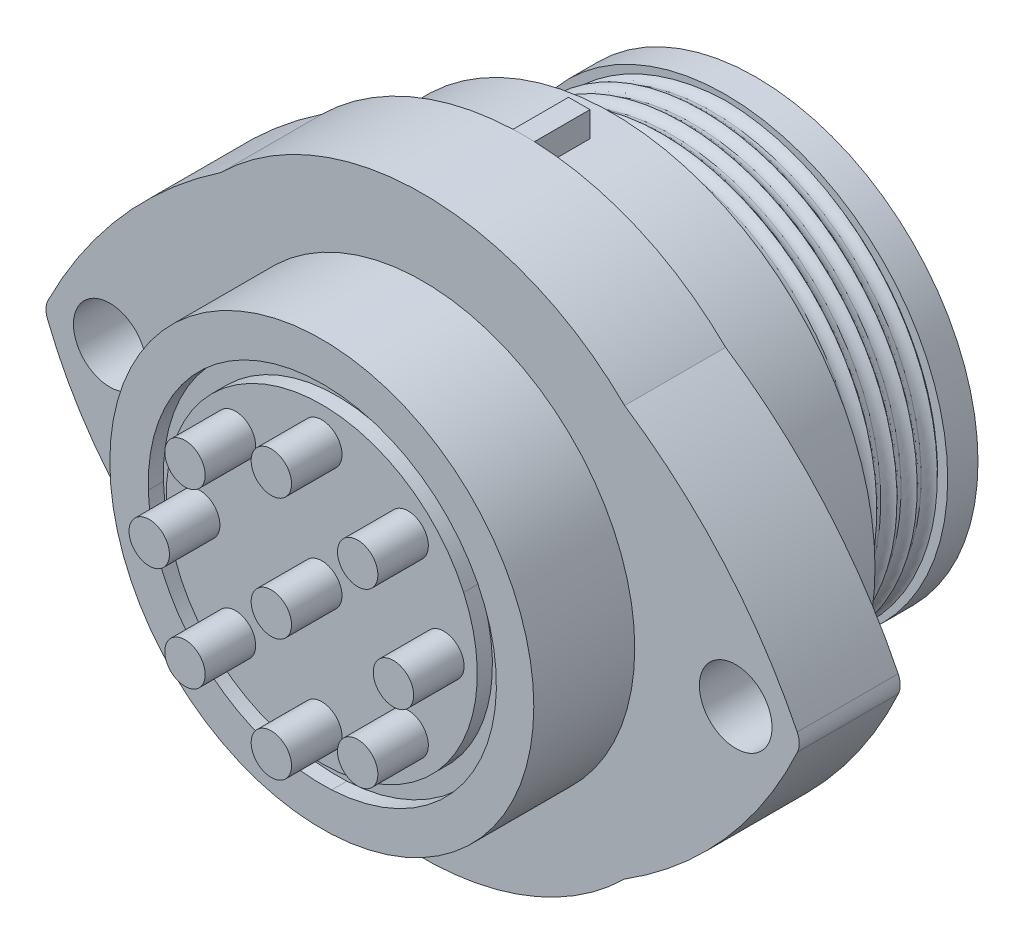
SolidWorks part; units mm, degrees
ref_plane "Front Plane" through (0, 0, 0) normal (0, 0, 1) x (1, 0, 0)
ref_plane "Top Plane" through (0, 0, 0) normal (0, 1, 0) x (1, 0, 0)
ref_plane "Right Plane" through (0, 0, 0) normal (1, 0, 0) x (0, 0, -1)
sketch "Sketch1" plane through (0, 0, 0) normal (0, 0, 1) x (1, 0, 0)
  circle A0 centre (0, 0) radius 10.5
  dimension "D1" = 21
extrude "Boss-Extrude1" add sketch "Sketch1" along normal blind 5
sketch "Sketch2" plane through (0, 0, 0) normal (0, 0, 1) x (1, 0, 0)
  arc A12 (9.9974, 10.1546) -> (-9.9974, 10.1546) centre (0, 0) ccw
  arc A13 (9.9974, 10.1546) -> (18.75, 0) centre (-3.668, -10.4735) cw
  arc A14 (18.75, 0) -> (9.9974, -10.1546) centre (-2.0445, 9.0742) cw
  arc A15 (-9.9974, 10.1546) -> (-18.75, 0) centre (4.3482, -11.0599) ccw
  arc A16 (-9.9974, -10.1546) -> (-18.75, 0) centre (-0.8564, 6.5738) cw
  arc A17 (-9.9974, -10.1546) -> (9.9974, -10.1546) centre (0, 0) ccw
  dimension "D1" = 28.5
  dimension "D2" = 18.75
  dimension "D3" = 18.75
extrude "Boss-Extrude2" add sketch "Sketch2" against normal blind 5
sketch "Sketch3" plane through (0, 0, -5) normal (0, 0, -1) x (-1, 0, 0)
  circle A2 centre (-15.5, 0) radius 1.8
  circle A3 centre (15.5, 0) radius 1.8
  dimension "D1" = 3.6
  dimension "D2" = 3.6
extrude "Cut-Extrude1" cut sketch "Sketch3" against normal blind 5
fillet "Fillet1" radius 1 2 edges at (-18.75, 0, -2.5) (18.75, 0, -2.5)
sketch "Sketch4" plane through (0, 0, 5) normal (0, 0, 1) x (1, 0, 0)
  circle A0 centre (0, 0) radius 1
  dimension "D1" = 2
extrude "Boss-Extrude5" add sketch "Sketch4" along normal blind 2.5
sketch "Sketch6" plane through (0, 0, 5) normal (0, 0, 1) x (1, 0, 0)
  circle A0 centre (0, 6.0476) radius 1
extrude "Boss-Extrude6" add sketch "Sketch6" along normal blind 2.5
pattern_circular "CirPattern2" count 8 over 360 about axis through (0, 0, 0) along (0, 0, 1) of "Boss-Extrude6"
sketch "Sketch7" plane through (0, 0, -5) normal (0, 0, -1) x (-1, 0, 0)
  circle A0 centre (0, 0) radius 13
  dimension "D1" = 26
extrude "Boss-Extrude7" add sketch "Sketch7" along normal blind 4.4
sketch "Sketch8" plane through (0, 0, -9.4) normal (0, 0, -1) x (-1, 0, 0)
  circle A0 centre (0, 0) radius 11
  dimension "D1" = 22
extrude "Boss-Extrude8" add sketch "Sketch8" along normal blind 5.6
sketch "Sketch12" plane through (0, 0, -15) normal (0, 0, -1) x (-1, 0, 0)
  circle A0 centre (0, 0) radius 11 construction
  circle A1 centre (0, 0) radius 11
curve "Helix/Spiral1" pitch 1 height 5.6 turns 5.6
sketch "Sketch13" plane through (0, 0, 0) normal (1, 0, 0) x (0, 0, -1)
  circle A0 centre (15, -11) radius 0.5649
sweep "Cut-Sweep1" cut profiles "Sketch13" path "Helix/Spiral1" align with end faces yes
sketch "Sketch14" plane through (0, 0, -15) normal (0, 0, -1) x (-1, 0, 0)
  circle A0 centre (0, 0) radius 11
  dimension "D1" = 22
extrude "Boss-Extrude9" add sketch "Sketch14" along normal blind 1.5
sketch "Sketch15" plane through (0, 0, -16.5) normal (0, 0, -1) x (-1, 0, 0)
  circle A0 centre (0, 0) radius 9.5
  dimension "D1" = 19
extrude "Cut-Extrude2" cut sketch "Sketch15" against normal blind 3.5
sketch "Sketch16" plane through (0, 0, -13) normal (0, 0, -1) x (-1, 0, 0)
  circle A0 centre (0, 0) radius 6.15
  dimension "D1" = 12.3
extrude "Boss-Extrude10" add sketch "Sketch16" along normal blind 5
sketch "Sketch17" plane through (0, 0, -18) normal (0, 0, -1) x (-1, 0, 0)
  circle A0 centre (0, 0) radius 1
  circle A1 centre (0, 3.43) radius 1
  dimension "D1" = 3.43
extrude "Cut-Extrude3" cut sketch "Sketch17" against normal blind 3
pattern_circular "CirPattern3" count 8 over 360 about axis through (0, 0, 0) along (0, 0, 1) of "Cut-Extrude3"
sketch "Sketch18" plane through (0, 0, -5) normal (0, 0, -1) x (-1, 0, 0)
  line L1 (0.5298, 12.9701) -> (-0.5298, 12.9701)
  line L2 (0.5298, 12.9701) -> (0.5298, 14.2401)
  line L3 (0.5298, 14.2401) -> (-0.5298, 14.2401)
  line L4 (-0.5298, 12.9701) -> (-0.5298, 14.2401)
  line L5 (0.5298, 12.9701) -> (-0.5298, 14.2401) construction
  line L6 (0.5298, 14.2401) -> (-0.5298, 12.9701) construction
  arc A0 (9.9974, 10.1546) -> (-9.9974, 10.1546) centre (0, 0) ccw construction
  point P0 (0, 13.6051)
  dimension "D1" = 1.27
extrude "Boss-Extrude11" add sketch "Sketch18" along normal blind 2.75
sketch "Sketch24" plane through (0, 0, 5) normal (0, 0, 1) x (1, 0, 0)
  arc A0 (-0.7464, 8.5675) -> (-8.5959, -0.267) centre (0, 0) ccw
  arc A1 (-8.5959, -0.267) -> (0.4877, -8.5844) centre (-0.0001, 0.0017) ccw
  arc A2 (0.4877, -8.5844) -> (8.6446, 0.237) centre (0.0478, 0.0043) ccw
  arc A3 (8.6446, 0.237) -> (-0.7464, 8.5675) centre (0.0478, 0.0043) ccw
  arc A4 (-7.6963, -0.239) -> (-6.9983, -3.2115) centre (0, 0) ccw
  arc A5 (-6.9983, -3.2115) -> (6.2082, -4.555) centre (0, 0) ccw
  arc A6 (6.2082, -4.555) -> (7.025, 3.1542) centre (0.0004, 0.0006) ccw
  arc A7 (7.025, 3.1542) -> (-7.6963, -0.239) centre (-0.0001, 0.0017) ccw
extrude "Cut-Extrude6" cut sketch "Sketch24" against normal blind 0.75
